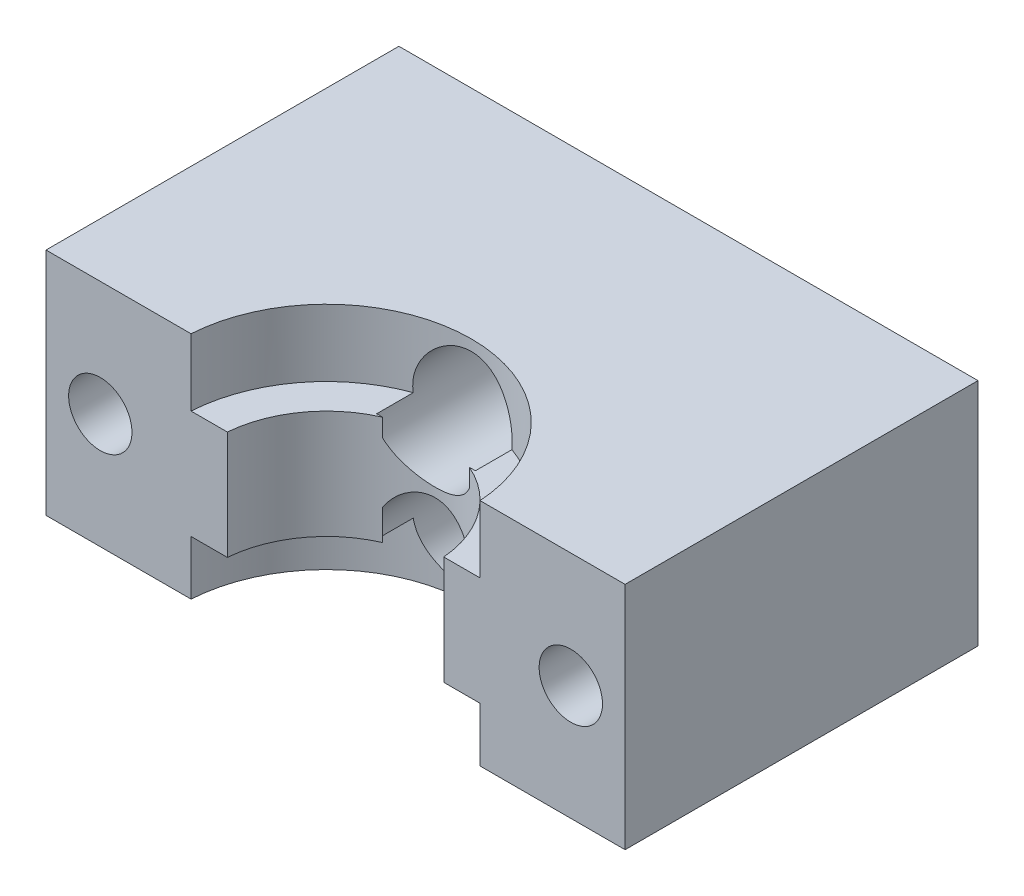
SolidWorks part; units mm, degrees
ref_plane "Front Plane" through (0, 0, 0) normal (0, 0, 1) x (1, 0, 0)
ref_plane "Top Plane" through (0, 0, 0) normal (0, 1, 0) x (1, 0, 0)
ref_plane "Right Plane" through (0, 0, 0) normal (1, 0, 0) x (0, 0, -1)
sketch "Sketch2" plane through (0, 0, 0) normal (0, 0, 1) x (1, 0, 0)
  line L0 (0, -3) -> (0, 3) construction
  line L1 (-16, 6.35) -> (16, 6.35)
  line L2 (-16, 6.35) -> (-16, -6.35)
  line L3 (-16, -6.35) -> (16, -6.35)
  line L4 (16, 6.35) -> (16, -6.35)
  line L5 (-16, 6.35) -> (16, -6.35) construction
  line L6 (-16, -6.35) -> (16, 6.35) construction
  circle A0 centre (0, 3) radius 1.75
  circle A1 centre (0, -3) radius 1.75
  point P0 (0, 0)
  dimension "D3" = 3.5
  dimension "D1" = 32
  dimension "D2" = 12.7
  dimension "D4" = 6
extrude "Boss-Extrude1" add sketch "Sketch2" along normal blind 19.5
sketch "Sketch3" plane through (0, 0, 19.5) normal (0, 0, 1) x (1, 0, 0)
  line L0 (16, 6.35) -> (-16, 6.35) construction
  line L5 (-16, -6.35) -> (16, -6.35) construction
  line L6 (-16, 6.35) -> (-10, 6.35) construction
  line L7 (-13, 6.35) -> (-13, -6.35) construction
  line L8 (10, 6.35) -> (16, 6.35) construction
  line L9 (13, 6.35) -> (13, -6.35) construction
  circle A0 centre (-13, 0) radius 1.75
  circle A1 centre (13, 0) radius 1.75
  dimension "D2" = 3.5
  dimension "D1" = 6
  dimension "D3" = 6
extrude "Cut-Extrude1" cut sketch "Sketch3" against normal through all
sketch "Sketch4" plane through (0, 0, 0) normal (0, 0, -1) x (-1, 0, 0)
  line L1 (-10.25, -1.5877) -> (-10.25, 1.5877)
  line L2 (-10.25, 1.5877) -> (-13, 3.1754)
  line L3 (-13, 3.1754) -> (-15.75, 1.5877)
  line L4 (-15.75, 1.5877) -> (-15.75, -1.5877)
  line L5 (-15.75, -1.5877) -> (-13, -3.1754)
  line L6 (-13, -3.1754) -> (-10.25, -1.5877)
  line L7 (13, -3.1754) -> (15.75, -1.5877)
  line L8 (15.75, -1.5877) -> (15.75, 1.5877)
  line L9 (15.75, 1.5877) -> (13, 3.1754)
  line L10 (13, 3.1754) -> (10.25, 1.5877)
  line L11 (10.25, 1.5877) -> (10.25, -1.5877)
  line L12 (10.25, -1.5877) -> (13, -3.1754)
  line L13 (-16, -6.35) -> (-16, 6.35) construction
  circle A0 centre (-13, 0) radius 2.75 construction
  circle A1 centre (13, 0) radius 2.75 construction
  dimension "D1" = 5.5
extrude "Cut-Extrude2" cut sketch "Sketch4" against normal blind 4
sketch "Sketch5" plane through (0, 6.35, 0) normal (0, 1, 0) x (1, 0, 0)
  line L0 (16, 0) -> (-16, 0) construction
  circle A0 centre (0, -20) radius 8
  dimension "D1" = 16
  dimension "D2" = 20
extrude "Cut-Extrude3" cut sketch "Sketch5" against normal blind 3.7
sketch "Sketch9" plane through (0, 2.65, 0) normal (0, 1, 0) x (1, 0, 0)
  circle A0 centre (0, -20) radius 6
  dimension "D1" = 12
extrude "Cut-Extrude5" cut sketch "Sketch9" against normal blind 6
sketch "Sketch10" plane through (0, -3.35, 0) normal (0, 1, 0) x (1, 0, 0)
  circle A0 centre (0, -20) radius 8
  dimension "D1" = 16
extrude "Cut-Extrude6" cut sketch "Sketch10" against normal through all
ref_plane "Plane1" through (0, 0, 14.5) normal (0, 0, 1) x (1, 0, 0)
sketch "Sketch6" plane through (0, 0, 14.5) normal (0, 0, 1) x (1, 0, 0)
  circle A0 centre (0, 3) radius 2.75
  circle A1 centre (0, -3) radius 2.75
  dimension "D1" = 5.5
  dimension "D2" = 5.5
extrude "Cut-Extrude4" cut sketch "Sketch6" against normal blind 7.5
